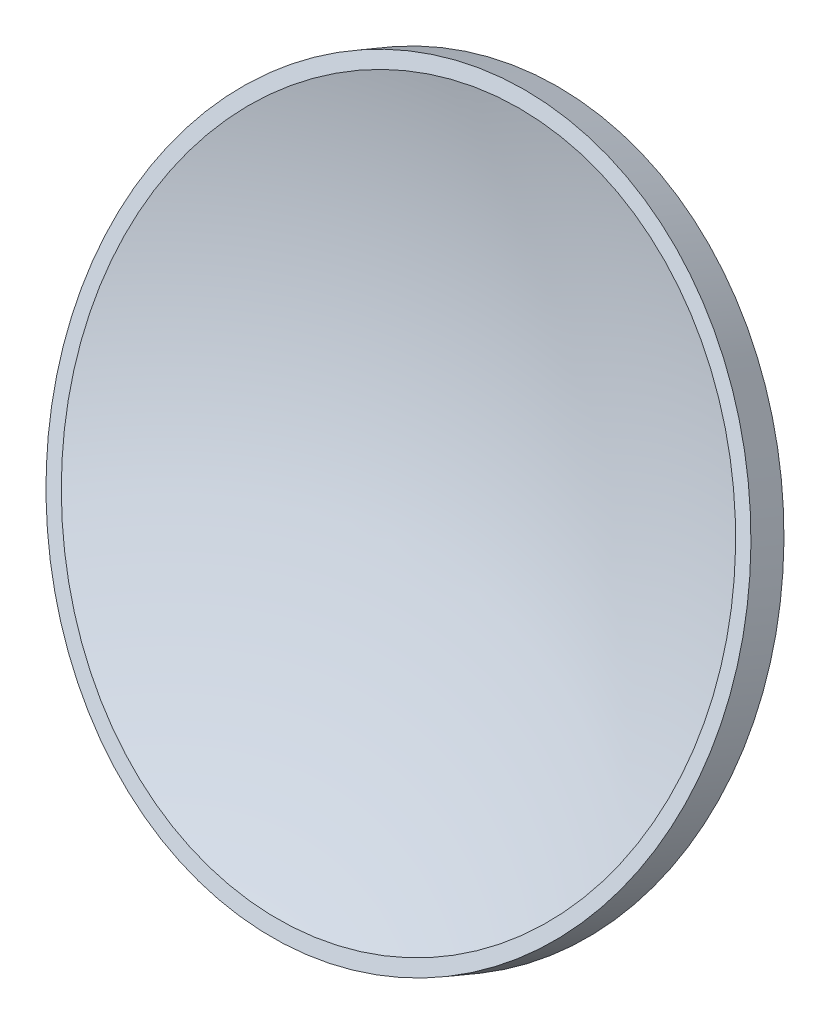
SolidWorks part; units mm, degrees
ref_plane "Plan de face" through (0, 0, 0) normal (0, 0, 1) x (1, 0, 0)
ref_plane "Plan de dessus" through (0, 0, 0) normal (0, 1, 0) x (1, 0, 0)
ref_plane "Plan de droite" through (0, 0, 0) normal (1, 0, 0) x (0, 0, -1)
ref_plane "Plan1" through (0, -1.4222, 0.591) normal (0, -0.9234, 0.3838) x (1, 0, 0)
sketch "Esquisse1" plane through (0, -1.4222, 0.591) normal (0, -0.9234, 0.3838) x (1, 0, 0)
  line L0 (0, 5.6558) -> (0, 0)
  line L1 (45.5, 8.9606) -> (46, 9.4606)
  line L2 (46, 9.4606) -> (46, 14.4606)
  line L3 (44.0004, 14.4606) -> (46, 14.4606)
  line L4 (0, 120) -> (0, 0) construction
  line L5 (45.5, 14.4606) -> (1.6857, 14.4606) construction
  arc A1 (0, 0) -> (45.5, 8.9606) centre (0, 120) ccw
  arc A2 (44.0004, 14.4606) -> (0, 5.6558) centre (0, 120) cw
  dimension "D2" = 5
  dimension "D3" = 120
  dimension "D4" = 0.5
  dimension "D6" = 114.3442
  dimension "D1" = 92
  dimension "D5" = 0.5
revolve "Révolution1" add sketch "Esquisse1" angle 360 about L4 reverse direction yes
ref_axis "Axe1" through (0, 16.6387, 44.0507) along (0, -0.3838, -0.9234)
